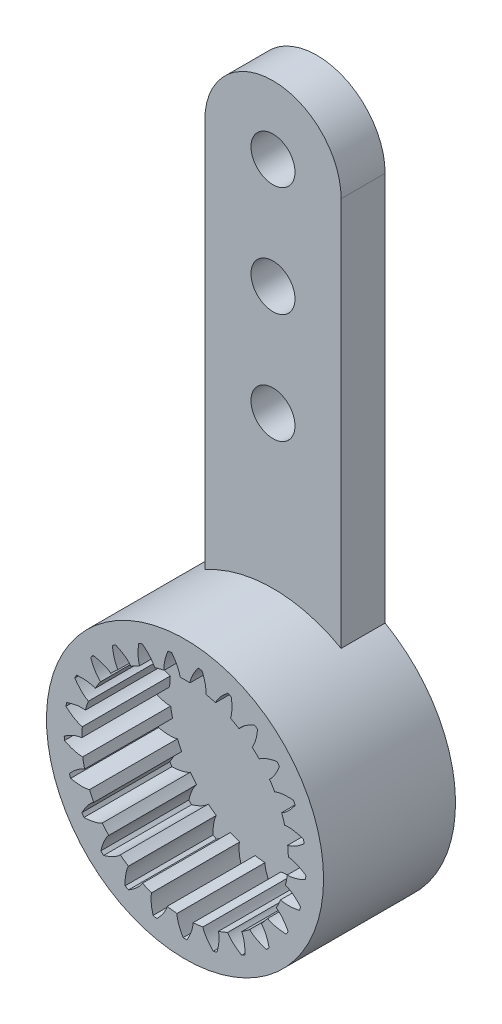
SolidWorks part; units mm, degrees
material "尼龙 101"
ref_plane "前视基准面" through (0, 0, 0) normal (0, 0, 1) x (1, 0, 0)
ref_plane "上视基准面" through (0, 0, 0) normal (0, 1, 0) x (1, 0, 0)
ref_plane "右视基准面" through (0, 0, 0) normal (1, 0, 0) x (0, 0, -1)
sketch "草图1" plane through (0, 0, 0) normal (0, 0, 1) x (1, 0, 0)
  circle A0 centre (0, 0) radius 2.75
  circle A1 centre (0, 0) radius 3.1508
extrude "凸台-拉伸1" add sketch "草图1" along normal blind 3
ref_axis "基准轴1" through (0, 0, 3) along (0, 0, -1)
sketch "草图2" plane through (0, 0, 0) normal (0, 0, 1) x (1, 0, 0)
  line L0 (0, 0) -> (0, 2.3492) construction
  arc A0 (0.1125, 2.3465) -> (-0.1125, 2.3465) centre (0, 0) ccw
  arc A1 (0.3518, 2.7954) -> (-0.3518, 2.7954) centre (0, 0) ccw
  spline S0 degree 3 poles (0.1125, 2.3465) (0.1128, 2.3506) (0.1136, 2.3564) (0.1148, 2.3642) (0.116, 2.3703) (0.1174, 2.3773) (0.1191, 2.3852) (0.1213, 2.394) (0.1239, 2.4036) (0.1269, 2.4141) (0.1304, 2.4254) (0.1344, 2.4375) (0.139, 2.4504) (0.1442, 2.4642) (0.15, 2.4787) (0.1564, 2.4939) (0.1635, 2.5099) (0.1714, 2.5265) (0.18, 2.5439) (0.1894, 2.5619) (0.1996, 2.5805) (0.2106, 2.5998) (0.2225, 2.6196) (0.2353, 2.64) (0.249, 2.6609) (0.2636, 2.6823) (0.2792, 2.7042) (0.2959, 2.7265) (0.3198, 2.7573) (0.3387, 2.7802) (0.3518, 2.7954) knots 0 0 0 0 0.023757 0.033985 0.046037 0.059914 0.075617 0.093145 0.112497 0.133675 0.156678 0.181506 0.208158 0.236637 0.26694 0.299068 0.333021 0.368799 0.406403 0.445831 0.487085 0.530164 0.575067 0.621796 0.67035 0.720729 0.772933 0.826962 0.882816 1 1 1 1
  spline S1 degree 3 poles (-0.1125, 2.3465) (-0.1128, 2.3506) (-0.1136, 2.3564) (-0.1148, 2.3642) (-0.116, 2.3703) (-0.1174, 2.3773) (-0.1191, 2.3852) (-0.1213, 2.394) (-0.1239, 2.4036) (-0.1269, 2.4141) (-0.1304, 2.4254) (-0.1344, 2.4375) (-0.139, 2.4504) (-0.1442, 2.4642) (-0.15, 2.4787) (-0.1564, 2.4939) (-0.1635, 2.5099) (-0.1714, 2.5265) (-0.18, 2.5439) (-0.1894, 2.5619) (-0.1996, 2.5805) (-0.2106, 2.5998) (-0.2225, 2.6196) (-0.2353, 2.64) (-0.249, 2.6609) (-0.2636, 2.6823) (-0.2792, 2.7042) (-0.2959, 2.7265) (-0.3198, 2.7573) (-0.3387, 2.7802) (-0.3518, 2.7954) knots 0 0 0 0 0.023757 0.033985 0.046037 0.059914 0.075617 0.093145 0.112497 0.133675 0.156678 0.181506 0.208158 0.236637 0.26694 0.299068 0.333021 0.368799 0.406403 0.445831 0.487085 0.530164 0.575067 0.621796 0.67035 0.720729 0.772933 0.826962 0.882816 1 1 1 1
extrude "凸台-拉伸2" add sketch "草图2" along normal blind 3
pattern_circular "阵列(圆周)1" count 25 every 14.4 about axis through (0, 0, 3) along (0, 0, -1) of "凸台-拉伸2"
sketch "草图3" plane through (0, 0, 0) normal (0, 0, 1) x (1, 0, 0)
  line L0 (0, 0) -> (0, 11.6) construction
  line L1 (-1.55, 11.6) -> (-1.55, 2.5686)
  line L2 (1.55, 11.6) -> (1.55, 2.5686)
  circle A0 centre (0, 0) radius 2.5 construction
  arc A1 (-1.55, 2.5686) -> (1.55, 2.5686) centre (0, 0) ccw
  circle A8 centre (0, 11.6) radius 0.5
  circle A9 centre (0, 9.1) radius 0.5
  circle A10 centre (0, 6.6) radius 0.5
  arc A13 (1.55, 11.6) -> (-1.55, 11.6) centre (0, 11.6) ccw
  dimension "Dn" = 5
  dimension "D1" = 3.1
  dimension "D2" = 6
  dimension "D4" = 1
  dimension "D3" = 11.6
  dimension "D5" = 3
extrude "凸台-拉伸3" add sketch "草图3" along normal blind 1
